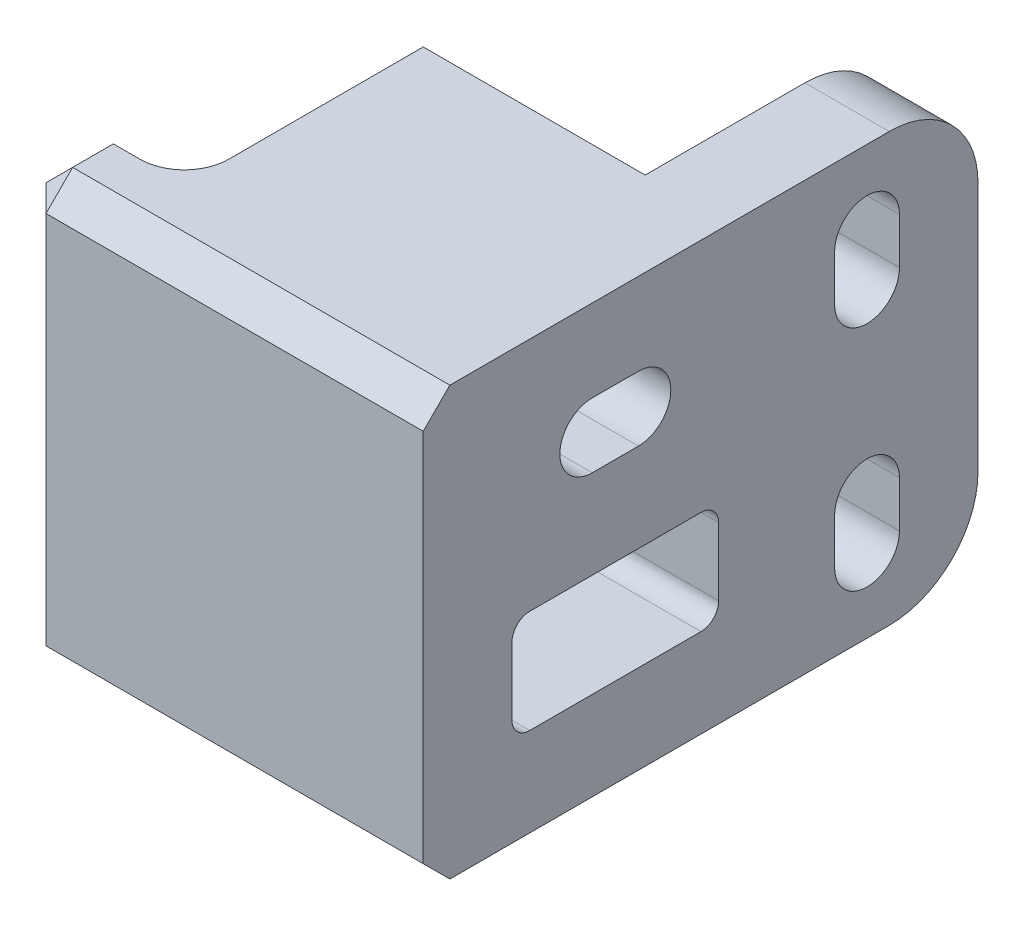
SolidWorks part; units mm, degrees
material "PET"
ref_plane "Front Plane" through (0, 0, 0) normal (0, 0, 1) x (1, 0, 0)
ref_plane "Top Plane" through (0, 0, 0) normal (0, 1, 0) x (1, 0, 0)
ref_plane "Right Plane" through (0, 0, 0) normal (1, 0, 0) x (0, 0, -1)
sketch "Sketch1" plane through (0, 0, 0) normal (0, 0, 1) x (1, 0, 0)
  line L0 (50.038, -17.5262) -> (50.038, -19.002) construction
  line L1 (56.388, -14.224) -> (50.038, -14.224)
  line L2 (56.388, -14.224) -> (56.388, -26.464)
  line L3 (56.388, -26.464) -> (50.038, -26.464)
  line L4 (50.038, -14.224) -> (50.038, -26.464)
  line L5 (56.388, -14.224) -> (50.038, -26.464) construction
  line L6 (56.388, -26.464) -> (50.038, -14.224) construction
  line L7 (48.738, -25.702) -> (50.788, -25.702) construction
  line L9 (56.388, -13.462) -> (35.687, -13.462) construction
  line L10 (56.388, -39.6174) -> (56.388, -13.462) construction
  point P4 (53.213, -20.344)
  dimension "D1" = 0.762
  dimension "D3" = 0.762
extrude "Boss-Extrude1" add sketch "Sketch1" along normal blind 8.255
sketch "Sketch2" plane through (50.038, 0, 0) normal (-1, 0, 0) x (0, 0, 1)
  line L0 (8.255, -14.224) -> (0, -14.224) construction
  line L1 (9.525, -26.464) -> (6.836, -26.464)
  line L2 (9.525, -26.464) -> (9.525, -14.224)
  line L3 (9.525, -14.224) -> (6.836, -14.224)
  line L4 (6.836, -26.464) -> (6.836, -23.46)
  line L5 (6.878, -22.952) -> (6.203, -22.952) construction
  line L6 (6.836, -23.46) -> (8.148, -23.46)
  line L8 (8.255, -26.464) -> (0, -26.464) construction
  line L9 (6.328, -24.652) -> (6.328, -25.5495) construction
  line L10 (8.255, -14.224) -> (8.255, -26.464) construction
  line L12 (6.836, -20.644) -> (8.148, -20.644)
  line L13 (8.148, -23.46) -> (8.148, -20.644)
  line L14 (6.328, -21.152) -> (6.878, -21.152) construction
  line L15 (6.878, -22.552) -> (6.878, -22.952) construction
  line L16 (6.836, -20.644) -> (6.836, -14.224)
  dimension "D1" = 0.508
  dimension "D2" = 1.27
  dimension "D3" = 0.508
  dimension "D4" = 0.508
  dimension "D5" = 1.27
extrude "Boss-Extrude2" add sketch "Sketch2" along normal blind 2.032 and the other way through all
sketch "Sketch3" plane through (0, -26.464, 0) normal (0, -1, 0) x (1, 0, 0)
  line L0 (50.038, 6.836) -> (50.038, 0) construction
  line L1 (50.038, 4.07) -> (51.496, 4.07)
  line L2 (50.038, 4.07) -> (50.038, 6.286)
  line L3 (50.038, 6.286) -> (51.496, 6.286)
  line L4 (51.496, 4.07) -> (51.496, 6.286)
  line L5 (49.988, 4.578) -> (50.788, 4.578) construction
  line L6 (50.788, 5.778) -> (49.988, 5.778) construction
  line L7 (50.988, 5.4426) -> (50.988, 4.9134) construction
  dimension "D1" = 0.508
  dimension "D2" = 0.508
  dimension "D3" = 0.508
extrude "Cut-Extrude1" cut sketch "Sketch3" against normal blind 3.81
sketch "Sketch9" plane through (56.388, 0, 0) normal (1, 0, 0) x (0, 0, -1)
  line L0 (0, -26.464) -> (0, -14.224) construction
  line L1 (-9.525, -14.224) -> (6.35, -14.224)
  line L2 (-9.525, -14.224) -> (-9.525, -26.464)
  line L3 (-9.525, -26.464) -> (6.35, -26.464)
  line L4 (6.35, -14.224) -> (6.35, -26.464)
  dimension "D1" = 6.35
extrude "Boss-Extrude3" add sketch "Sketch9" along normal blind 3.175
fillet "Fillet2" radius 2.54 2 edges at (57.9755, -14.224, -6.35) (57.9755, -26.464, -6.35)
hole_wizard "#0 Clearance Slot1" positions "Sketch5" profile "Sketch4" size "#0" standard "ANSI Inch" slot yes end condition through all
sketch "Sketch5" plane through (59.563, 0, 0) normal (1, 0, 0) x (0, 0, -1)
  line L0 (-2.4405, -17.5047) -> (-5.6155, -17.5047) construction
  point P0 (-4.028, -17.5047)
  dimension "D1" = 3.175
sketch "Sketch4" plane through (59.563, -17.5047, 4.028) normal (0, 1, 0) x (0, 0, -1)
  line L0 (0, 0) -> (0, 11.557)
  line L1 (0, 11.557) -> (0.9271, 11.557)
  line L2 (0.9271, 11.557) -> (0.9271, 0)
  line L5 (0.9271, 0) -> (0, 0)
  line L11 (0, -6.35) -> (0, 107.95) construction
  dimension "Thru Hole Dia." = 1.8542
  dimension "Thru Hole Depth" = 11.557
hole_wizard "#0 Clearance Slot2" positions "Sketch11" profile "Sketch10" size "#0" standard "ANSI Inch" slot yes end condition through all
sketch "Sketch11" plane through (59.563, 0, 0) normal (1, 0, 0) x (0, 0, -1)
  line L0 (3.175, -18.669) -> (3.175, -15.494) construction
  line L1 (3.81, -14.224) -> (-9.525, -14.224) construction
  line L2 (6.35, -20.344) -> (-9.525, -20.344) construction
  line L3 (6.35, -23.924) -> (6.35, -16.764) construction
  line L4 (-9.525, -14.224) -> (-9.525, -26.464) construction
  point P0 (3.175, -17.0815)
  point P19 (3.175, -23.6065)
  dimension "D1" = 3.175
  dimension "D2" = 1.27
  dimension "D3" = 3.175
sketch "Sketch10" plane through (59.563, -17.0815, -3.175) normal (0, 1, 0) x (0, 0, -1)
  line L0 (0, 0) -> (0, 11.557)
  line L1 (0, 11.557) -> (0.9271, 11.557)
  line L2 (0.9271, 11.557) -> (0.9271, 0)
  line L5 (0.9271, 0) -> (0, 0)
  line L11 (0, -6.35) -> (0, 107.95) construction
  dimension "Thru Hole Dia." = 1.8542
  dimension "Thru Hole Depth" = 11.557
fillet "Fillet3" radius 0.508 12 edges at (50.038, -17.434, 6.836) (50.038, -24.962, 6.836) (49.022, -20.644, 8.148) (50.038, -20.644, 7.492) (50.038, -22.052, 8.148) (49.022, -23.46, 8.148) (50.038, -23.46, 7.492) (50.767, -22.654, 4.07) (50.767, -22.654, 6.286) (51.496, -22.654, 5.178) (51.496, -24.559, 4.07) (51.496, -24.559, 6.286)
chamfer "Chamfer3" distance 0.762 angle 45 23 edges at (48.768, -14.224, 6.836) (49.8892, -14.224, 6.6872) (50.038, -14.224, 3.164) (49.8892, -26.464, 6.6872) (53.7845, -26.464, 9.525) (53.7845, -14.224, 9.525) (48.006, -14.224, 8.1805) (48.006, -20.344, 9.525) (48.006, -26.464, 8.1805) (48.768, -26.464, 6.836) (50.513, -26.464, 6.286) (56.388, -14.9679, -5.6061) (51.3472, -26.464, 6.1372) (56.388, -20.344, -6.35) (51.496, -26.464, 5.178) (56.388, -25.7201, -5.6061) (51.3472, -26.464, 4.2188) (50.513, -26.464, 4.07) (50.038, -26.464, 2.035)
sketch "Sketch12" plane through (59.563, 0, 0) normal (1, 0, 0) x (0, 0, -1)
  line L0 (-4.028, -18.4318) -> (-4.028, -26.464) construction
  line L1 (-3.3676, -18.4318) -> (-4.6884, -18.4318) construction
  line L2 (-8.763, -26.464) -> (3.81, -26.464) construction
  line L3 (-9.525, -14.986) -> (-9.525, -25.702) construction
  line L4 (-6.985, -20.9718) -> (-1.071, -20.9718)
  line L5 (-6.985, -20.9718) -> (-6.985, -23.924)
  line L6 (-6.985, -23.924) -> (-1.071, -23.924)
  line L7 (-1.071, -20.9718) -> (-1.071, -23.924)
  line L8 (-6.985, -20.9718) -> (-1.071, -23.924) construction
  line L9 (-6.985, -23.924) -> (-1.071, -20.9718) construction
  point P6 (-4.028, -22.4479)
  dimension "D1" = 2.54
  dimension "D2" = 2.54
extrude "Cut-Extrude2" cut sketch "Sketch12" against normal through all
fillet "Fillet4" radius 0.508 4 edges at (53.7845, -23.924, 6.985) (54.8005, -23.924, 1.071) (54.8005, -20.9718, 1.071) (54.784, -20.9718, 6.985)
